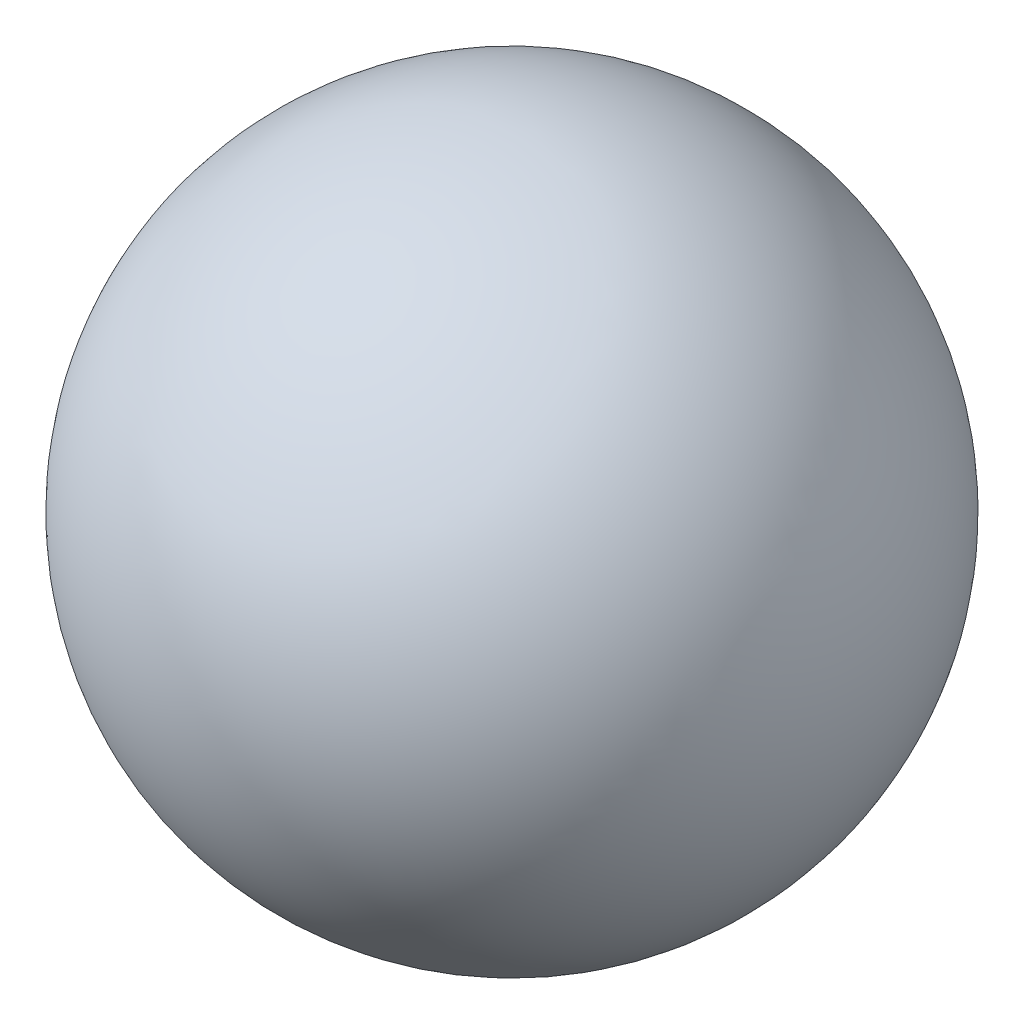
SolidWorks part; units mm, degrees
ref_plane "Front Plane" through (0, 0, 0) normal (0, 0, 1) x (1, 0, 0)
ref_plane "Top Plane" through (0, 0, 0) normal (0, 1, 0) x (1, 0, 0)
ref_plane "Right Plane" through (0, 0, 0) normal (1, 0, 0) x (0, 0, -1)
sketch "Sketch1" plane through (0, 0, 0) normal (0, 0, 1) x (1, 0, 0)
  line L0 (-12, 0) -> (12, 0)
  arc A0 (12, 0) -> (-12, 0) centre (0, 0) cw
  dimension "D1" = 24
revolve "Revolve1" add sketch "Sketch1" angle 360 about L0
scale "Scale1" scale about centroid uniform scaling yes scale factor 0.07
